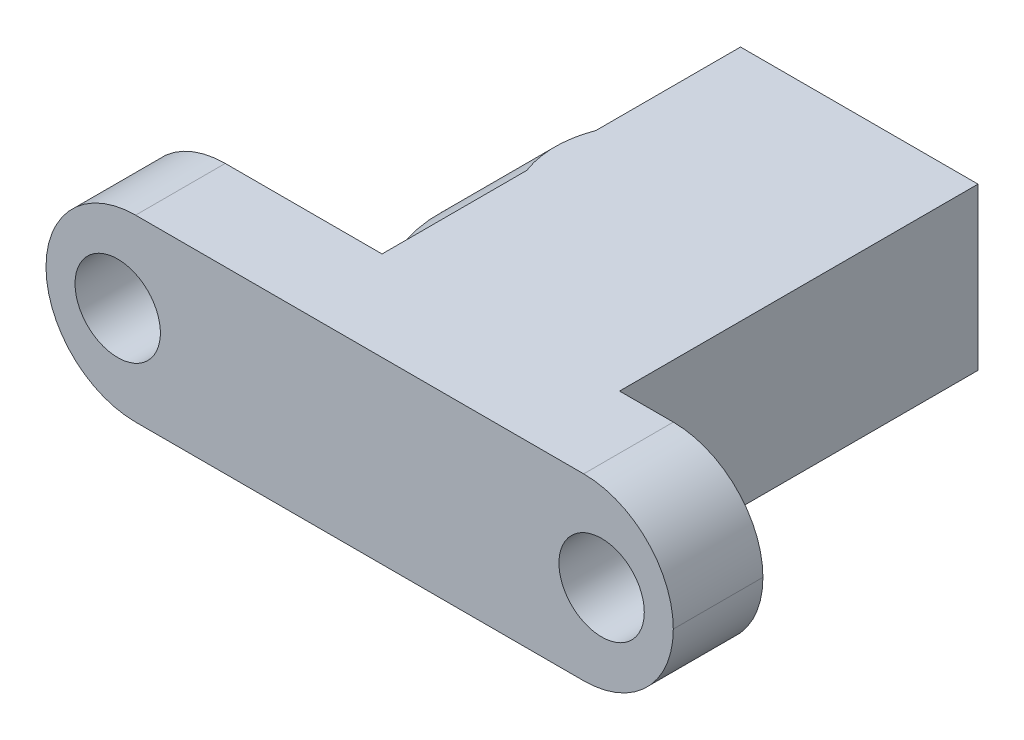
SolidWorks part; units mm, degrees
material "ABS"
ref_plane "Front" through (0, 0, 0) normal (0, 0, 1) x (1, 0, 0)
ref_plane "Top" through (0, 0, 0) normal (0, 1, 0) x (1, 0, 0)
ref_plane "Right" through (0, 0, 0) normal (1, 0, 0) x (0, 0, -1)
sketch "Sketch1" plane through (0, 0, 0) normal (0, 0, 1) x (1, 0, 0)
  line L0 (0, 21.3333) -> (0, -21.3333) construction
  line L1 (-13.5, 0) -> (13.5, 0) construction
  line L2 (-17.5, -5) -> (17.5, -5)
  line L3 (-17.5, -5) -> (-17.5, 5)
  line L4 (-17.5, 5) -> (17.5, 5)
  line L5 (17.5, -5) -> (17.5, 5)
  line L6 (-17.5, -5) -> (17.5, 5) construction
  line L7 (-17.5, 5) -> (17.5, -5) construction
  circle A0 centre (13.5, 0) radius 2.3813
  circle A1 centre (-13.5, 0) radius 2.3813
  point P4 (0, 0)
  point P7 (0, 0)
  dimension "D1" = 4.7625
  dimension "D2" = 35
  dimension "D3" = 10
  dimension "D4" = 4
  dimension "D5" = 27
extrude "Boss-Extrude1" add sketch "Sketch1" along normal blind 5
sketch "Sketch2" plane through (0, 0, 0) normal (0, 0, -1) x (-1, 0, 0)
  line L0 (-17.5, 5) -> (17.5, 5) construction
  line L1 (-9.5, -4) -> (2.5, -4)
  line L2 (-9.5, -4) -> (-9.5, 4)
  line L4 (2.5, -4) -> (2.5, 4)
  line L5 (-3.5, 0) -> (2.5, 0) construction
  line L6 (-3.5, 0) -> (-9.5, 0) construction
  line L8 (-9.5, 4) -> (-9.5, 5)
  line L9 (-9.5, 5) -> (2.5, 5)
  line L10 (2.5, 4) -> (2.5, 5)
  line L11 (-3.5, 0) -> (13.5, 0) construction
  point P0 (0, 0)
  dimension "D1" = 8
  dimension "D2" = 12
  dimension "D3" = 17
extrude "Boss-Extrude2" add sketch "Sketch2" along normal blind 20
ref_plane "Plane1" through (-3.25, -3.25, 0) normal (-0.7071, -0.7071, 0) x (0, 0, 1)
sketch "Sketch3" plane through (-3.25, -3.25, 0) normal (-0.7071, -0.7071, 0) x (0, 0, 1)
  line L0 (-20, -1.0607) -> (0, -1.0607) construction
  line L1 (0, 8.8388) -> (0, -15.9099) construction
  circle A0 centre (-10, -1.0607) radius 5.5
  dimension "D1" = 11
  dimension "D2" = 10
extrude "Cut-Extrude1" cut sketch "Sketch3" against normal blind 6
sketch "Sketch4" plane through (0.9926, 0.9926, 0) normal (-0.7071, -0.7071, 0) x (0, 0, 1)
  circle A0 centre (-10, -1.0607) radius 5.5
  circle A2 centre (-10, -1.0607) radius 7.5
  dimension "D1" = 2
extrude "Boss-Extrude3" add sketch "Sketch4" along normal blind 10
fillet "Fillet1" radius 5 4 edges at (17.5, 5, 2.5) (17.5, -5, 2.5) (-17.5, -5, 2.5) (-17.5, 5, 2.5)
sketch "Sketch5" plane through (0, 0, -20) normal (0, 0, -1) x (-1, 0, 0)
  line L1 (2.5, 4.4853) -> (3.75, 4.4853)
  line L2 (2.5, 4.4853) -> (2.5, 5)
  line L3 (2.5, 5) -> (3.75, 5)
  line L4 (3.75, 4.4853) -> (3.75, 5)
  dimension "D1" = 1.25
extrude "Boss-Extrude4" add sketch "Sketch5" against normal up to surface (20 mm away) up to face at (1.4, 0.2, 0)
sketch "Sketch6" plane through (0, 0, -20) normal (0, 0, -1) x (-1, 0, 0)
  line L1 (3.0147, 5) -> (9.6389, 5)
  line L2 (3.0147, 5) -> (3.0147, 5.6124)
  line L3 (3.0147, 5.6124) -> (9.6389, 5.6124)
  line L4 (9.6389, 5) -> (9.6389, 5.6124)
extrude "Cut-Extrude2" cut sketch "Sketch6" against normal through all
sketch "Sketch7" plane through (0, 0, -20) normal (0, 0, -1) x (-1, 0, 0)
  line L0 (12.5, -5) -> (-12.5, -5) construction
  line L1 (-5.9853, -4) -> (-7.1738, -4)
  line L2 (-5.9853, -4) -> (-5.9853, -5)
  line L3 (-5.9853, -5) -> (-7.1738, -5)
  line L4 (-7.1738, -4) -> (-7.1738, -5)
extrude "Boss-Extrude5" add sketch "Sketch7" against normal up to surface (20 mm away) up to face at (0.5417, 0.9142, 0)
